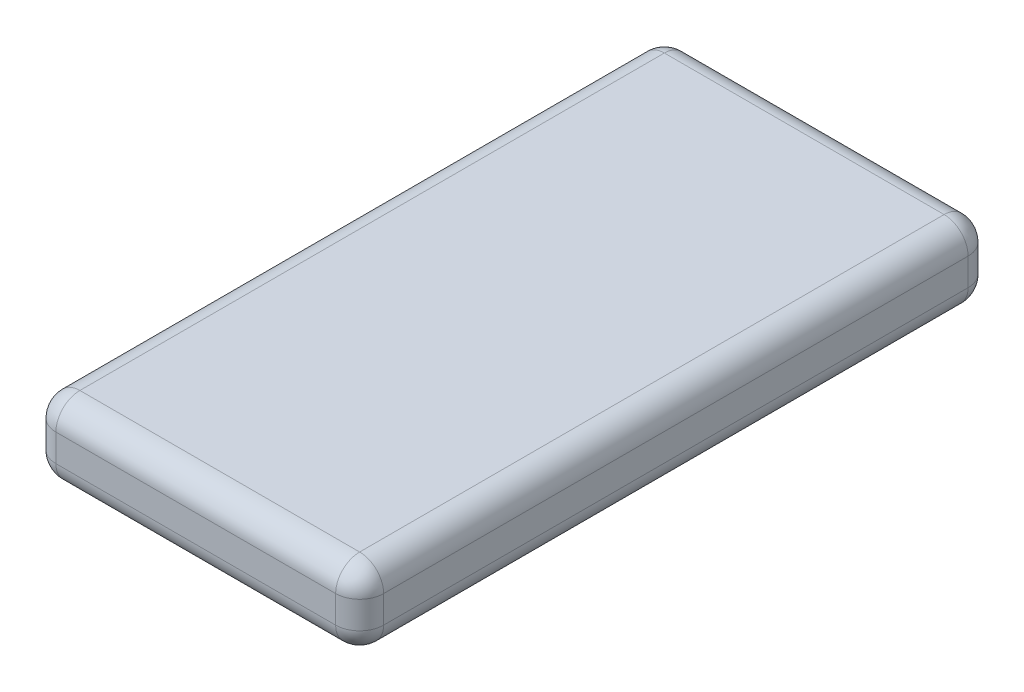
SolidWorks part; units mm, degrees
ref_plane "Front Plane" through (0, 0, 0) normal (0, 0, 1) x (1, 0, 0)
ref_plane "Top Plane" through (0, 0, 0) normal (0, 1, 0) x (1, 0, 0)
ref_plane "Right Plane" through (0, 0, 0) normal (1, 0, 0) x (0, 0, -1)
sketch "Sketch1" plane through (0, 0, 0) normal (0, 1, 0) x (1, 0, 0)
  line L1 (-34.15, -65.9) -> (34.15, -65.9)
  line L2 (-34.15, -65.9) -> (-34.15, 65.9)
  line L3 (-34.15, 65.9) -> (34.15, 65.9)
  line L4 (34.15, -65.9) -> (34.15, 65.9)
  line L5 (-34.15, -65.9) -> (34.15, 65.9) construction
  line L6 (-34.15, 65.9) -> (34.15, -65.9) construction
  point P0 (0, 0)
  dimension "D1" = 131.8
  dimension "D2" = 68.3
extrude "Boss-Extrude1" add sketch "Sketch1" along normal mid plane 15.7
fillet "Fillet1" radius 5 12 edges at (0, -7.85, -65.9) (0, -7.85, 65.9) (0, 7.85, 65.9) (0, 7.85, -65.9) (34.15, 0, 65.9) (34.15, 7.85, 0) (34.15, 0, -65.9) (34.15, -7.85, 0) (-34.15, 0, -65.9) (-34.15, 7.85, 0) (-34.15, 0, 65.9) (-34.15, -7.85, 0)
sketch "Sketch2" plane through (0, 0, -65.9) normal (0, 0, -1) x (-1, 0, 0)
  line L0 (-29.15, 2.85) -> (-29.15, -2.85) construction
  line L1 (-5, 5) -> (5, 5)
  line L2 (-5, 5) -> (-5, -5)
  line L3 (-5, -5) -> (5, -5)
  line L4 (5, 5) -> (5, -5)
  line L5 (-29.15, 0) -> (-5, 0) construction
  point P5 (0, -5)
  dimension "D1" = 10
  dimension "D2" = 10
extrude "Cut-Extrude1" cut sketch "Sketch2" against normal blind 10
